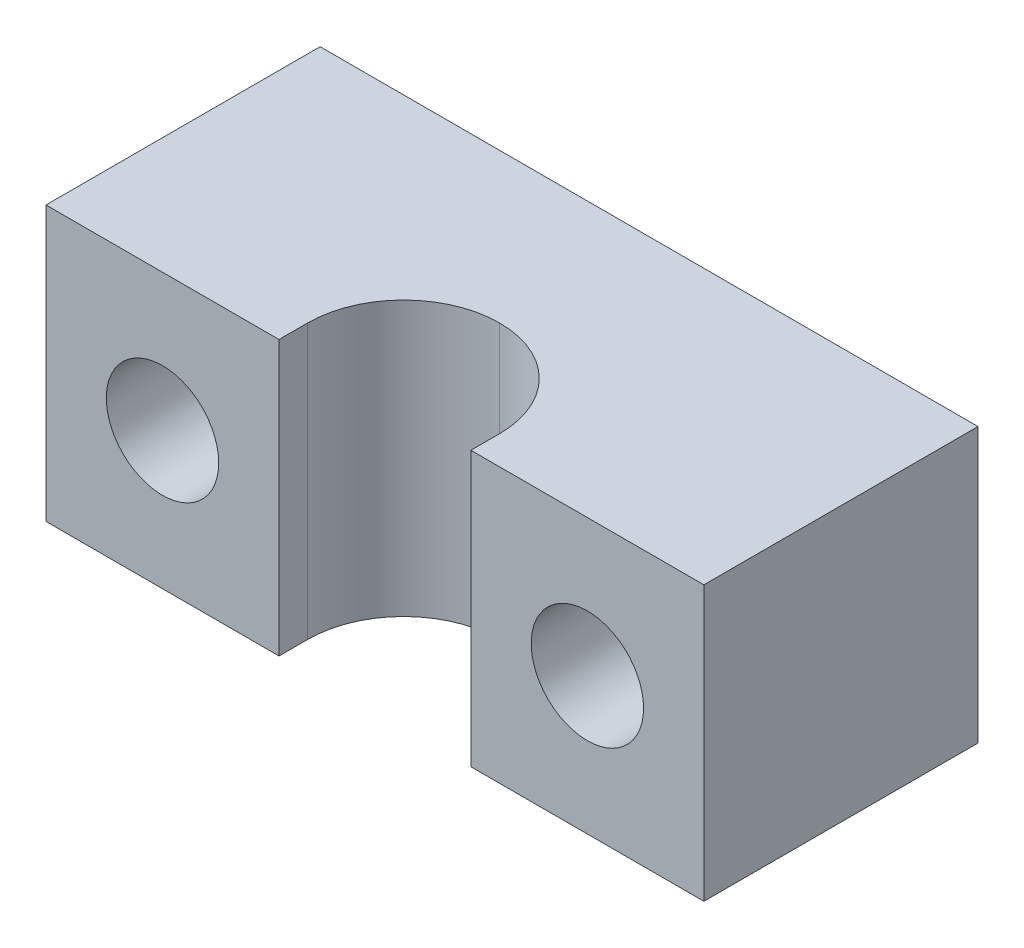
SolidWorks part; units mm, degrees
ref_plane "Спереди" through (0, 0, 0) normal (0, 0, 1) x (1, 0, 0)
ref_plane "Сверху" through (0, 0, 0) normal (0, 1, 0) x (1, 0, 0)
ref_plane "Справа" through (0, 0, 0) normal (1, 0, 0) x (0, 0, -1)
sketch "Sketch1" plane through (0, 0, 0) normal (0, 1, 0) x (1, 0, 0)
  line L0 (-22.986, 8.6014) -> (-22.986, -11.3986)
  line L1 (-22.986, -11.3986) -> (-5.986, -11.3986)
  line L2 (-5.986, -11.3986) -> (-5.986, -2.3077)
  line L3 (-5.986, -2.3077) -> (8.014, -2.3077)
  line L4 (8.014, -2.3077) -> (8.014, -11.3986)
  line L5 (8.014, -11.3986) -> (25.014, -11.3986)
  line L6 (25.014, -11.3986) -> (25.014, 8.6014)
  line L7 (25.014, 8.6014) -> (6.014, 8.6014)
  line L8 (6.014, 8.6014) -> (6.014, 58.6014)
  line L9 (6.014, 58.6014) -> (-3.986, 58.6014)
  line L10 (-3.986, 58.6014) -> (-3.986, 8.6014)
  line L11 (-3.986, 8.6014) -> (-22.986, 8.6014)
  dimension "D1" = 20
  dimension "D2" = 48
  dimension "D3" = 50
  dimension "D4" = 10
  dimension "D5" = 14
extrude "Boss-Extrude1" add sketch "Sketch1" along normal blind 20
sketch "Sketch3" plane through (0, 0, 11.3986) normal (0, 0, 1) x (1, 0, 0)
  line L0 (-22.986, 10) -> (-5.986, 10) construction
  line L1 (-22.986, 20) -> (-22.986, 0) construction
  line L2 (-5.986, 20) -> (-5.986, 0) construction
  line L4 (8.014, 10) -> (25.014, 10) construction
  line L5 (8.014, 20) -> (8.014, 0) construction
  line L6 (25.014, 20) -> (25.014, 0) construction
  circle A0 centre (-14.486, 10) radius 4.1
  circle A1 centre (16.514, 10) radius 4.1
  dimension "D1" = 8.2
extrude "Cut-Extrude1" cut sketch "Sketch3" against normal through all
sketch "Sketch4" plane through (6.014, 0, 0) normal (1, 0, 0) x (0, 0, -1)
  line L0 (58.6014, 10) -> (8.6014, 10) construction
  line L1 (58.6014, 20) -> (58.6014, 0) construction
  line L2 (8.6014, 20) -> (8.6014, 0) construction
  circle A0 centre (28.6014, 10) radius 4.1
  circle A1 centre (48.6014, 10) radius 4.1
  dimension "D1" = 8.2
  dimension "D2" = 20
  dimension "D3" = 20
extrude "Cut-Extrude2" cut sketch "Sketch4" against normal through all
fillet "Fillet1" radius 7 2 edges at (-5.986, 10, 2.3077) (8.014, 10, 2.3077)
sketch "Sketch6" plane through (0, 20, 0) normal (0, 1, 0) x (1, 0, 0)
  line L0 (-3.986, 8.6014) -> (6.014, 8.6014)
  line L1 (6.014, 8.6014) -> (6.014, 58.6014)
  line L2 (6.014, 58.6014) -> (-3.986, 58.6014)
  line L3 (-3.986, 58.6014) -> (-3.986, 8.6014)
extrude "Cut-Extrude3" cut sketch "Sketch6" against normal through all
